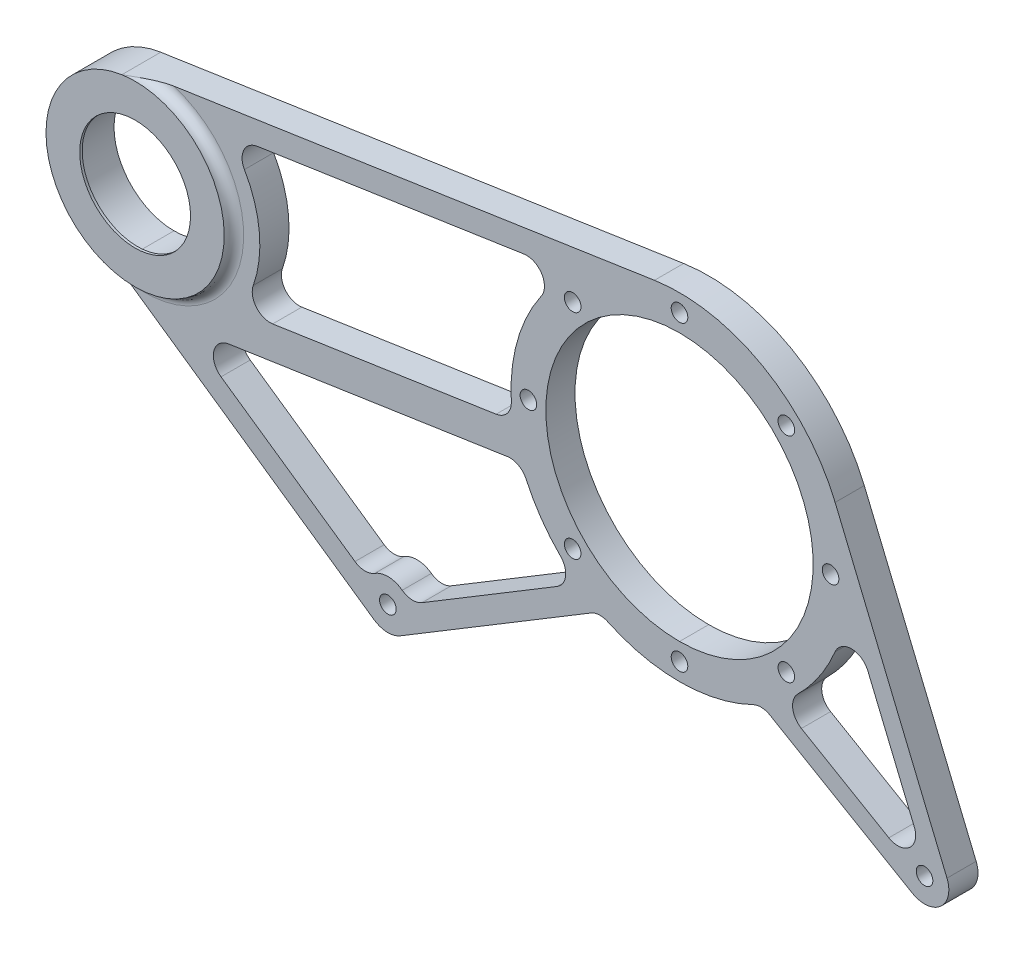
SolidWorks part; units mm, degrees
material "6061-T6 (SS)"
ref_plane "Front Plane" through (0, 0, 0) normal (0, 0, 1) x (1, 0, 0)
ref_plane "Top Plane" through (0, 0, 0) normal (0, 1, 0) x (1, 0, 0)
ref_plane "Right Plane" through (0, 0, 0) normal (1, 0, 0) x (0, 0, -1)
sketch "Sketch1" plane through (0, 0, 0) normal (0, 0, 1) x (1, 0, 0)
  line L0 (-329.0358, 136.1378) -> (-124.1059, 166.9079)
  line L1 (-343.7594, 72.9056) -> (-234.0298, -3.2296)
  line L2 (-223.6766, -3.5577) -> (-149.0272, 41.5159)
  line L3 (-114.3, 88.9) -> (-114.3, 101.6) construction
  line L4 (-53.3056, 126.9173) -> (-9.4675, 21.3025)
  line L5 (-23.0618, 9.4221) -> (-78.8665, 41.9532)
  circle A0 centre (-114.3, 88.9) radius 82.9716 construction
  circle A1 centre (-228.6, -20.8038) radius 12.7 construction
  circle A2 centre (0, 0) radius 12.7 construction
  circle A3 centre (-323.85, 101.6) radius 114 construction
  circle A4 centre (-323.85, 101.6) radius 23.5
  circle A5 centre (-114.3, 101.6) radius 52.3875
  arc A6 (-142.4404, 41.8555) -> (-85.4371, 42.2012) centre (-114.3, 101.6) ccw
  circle A7 centre (-323.85, 101.6) radius 34.925
  arc A8 (-223.6766, -3.5577) -> (-234.0298, -3.2296) centre (-228.6, 4.5962) cw
  arc A9 (-9.4675, 21.3025) -> (-23.0618, 9.4221) centre (-18.2648, 17.651) cw
  circle A10 centre (-228.6, 4.5962) radius 3.2512
  circle A11 centre (-18.2648, 17.651) radius 3.2512
  arc A12 (-142.4404, 41.8555) -> (-149.0272, 41.5159) centre (-145.4168, 35.5364) ccw
  arc A13 (-78.8665, 41.9532) -> (-85.4371, 42.2012) centre (-82.3843, 35.9187) ccw
  circle A14 centre (-114.3, 101.6) radius 66.04 construction
  arc A15 (-124.1059, 166.9079) -> (-53.3056, 126.9173) centre (-114.3, 101.6) cw
  point P33 (-145.0631, 160.0372)
  dimension "D1" = 88.9
  dimension "D2" = 12.7
  dimension "D3" = 25.4
  dimension "D4" = 25.4
  dimension "D8" = 165.9433
  dimension "D9" = 228
  dimension "D10" = 47
  dimension "D12" = 104.775
  dimension "D14" = 132.08
  dimension "D15" = 69.85
  dimension "D16" = 9.525
  dimension "D18" = 9.525
  dimension "D20" = 6.5024
  dimension "D21" = 6.5024
  dimension "D23" = 6.985
  dimension "D24" = 6.985
  dimension "D25" = 66.04
  dimension "D5" = 228.6
  dimension "D6" = 20.8038
  dimension "D7" = 114.3
  dimension "D11" = 12.7
  dimension "D13" = 209.55
  dimension "D17" = 25.4
  dimension "D19" = 25.4
  dimension "D22" = 17.651
extrude "Boss-Extrude1" add sketch "Sketch1" along normal blind 11.43 contours A7 A4 | A8 L2 A6 L0 A7 L1 A10 | A6 A5 | A9 L4 A6 L5 A11 region at (-187.4243, 81.6254, 0) region at (-301.706, 127.3172, 0)
ref_point "Point2"
ref_point "Point4"
ref_plane "Plane2" through (-114.3, 0, 0) normal (1, 0, 0) x (0, 0, -1)
ref_plane "Plane3" through (-323.85, 0, 0) normal (1, 0, 0) x (0, 0, -1)
sketch "Sketch5" plane through (0, 0, 11.43) normal (0, 0, 1) x (1, 0, 0)
  circle A0 centre (-323.85, 101.6) radius 23.5
  circle A1 centre (-323.85, 101.6) radius 34.925
extrude "Boss-Extrude3" add sketch "Sketch5" along normal blind 3.81
fillet "Fillet2" radius 3.81 1 edges at (-289.835, 93.6796, 11.43)
sketch "Sketch6" plane through (0, 0, 15.24) normal (0, 0, 1) x (1, 0, 0)
  circle A0 centre (-323.85, 101.6) radius 23.5
  circle A1 centre (-323.85, 101.6) radius 21.722
  dimension "D1" = 47
  dimension "D2" = 1.778
extrude "Boss-Extrude4" add sketch "Sketch6" against normal blind 0.9677
split line "Split Line3"
split line "Split Line4"
sketch "Sketch7" plane through (0, 0, 0) normal (0, 0, 1) x (1, 0, 0)
  line L0 (-279.7929, 134.542) -> (-175.2648, 150.2368)
  line L1 (-300.8405, 140.3714) -> (-125.2445, 166.737)
  line L2 (-312.4691, 138.6253) -> (-124.1059, 166.9079) construction
  line L3 (-329.9956, 63.3556) -> (-234.0298, -3.2296) construction
  line L4 (-329.9956, 63.3556) -> (-320.3344, 56.6523) construction
  line L5 (-293.9898, 49.1936) -> (-241.4832, 12.7622)
  line L6 (-215.2255, 11.93) -> (-162.2555, 43.9136)
  line L7 (-223.6766, -3.5577) -> (-149.0272, 41.5159) construction
  line L8 (-223.6766, -3.5577) -> (-149.0272, 41.5159) construction
  line L9 (-291.0451, 61.84) -> (-181.7958, 78.2437)
  line L10 (-273.7403, 77.2807) -> (-186.1633, 90.4303)
  line L11 (-32.2583, 23.6034) -> (-66.5305, 43.5822)
  line L12 (-22.2892, 32.3156) -> (-40.471, 76.1193)
  line L13 (-23.0618, 9.4221) -> (-78.8665, 41.9532) construction
  line L14 (-53.3056, 126.9173) -> (-9.4675, 21.3025) construction
  line L15 (-23.0618, 9.4221) -> (-78.8665, 41.9532) construction
  line L16 (-53.3056, 126.9173) -> (-9.4675, 21.3025) construction
  line L17 (-312.4691, 138.6253) -> (-124.1059, 166.9079) construction
  circle A0 centre (-114.3, 101.6) radius 62.0284 construction
  circle A1 centre (-323.85, 101.6) radius 38.735 construction
  circle A2 centre (-323.85, 101.6) radius 45.085 construction
  arc A4 (-291.0451, 61.84) -> (-293.9898, 49.1936) centre (-290.0079, 54.9325) ccw
  arc A5 (-174.4017, 74.231) -> (-160.9335, 54.839) centre (-114.3, 101.6) ccw
  arc A6 (-160.9335, 54.839) -> (-162.2555, 43.9136) centre (-165.8659, 49.8931) cw
  arc A7 (-181.7958, 78.2437) -> (-174.4017, 74.231) centre (-180.7586, 71.3362) cw
  arc A8 (-284.805, 124.142) -> (-281.3603, 86.524) centre (-323.85, 101.6) cw
  arc A9 (-168.4954, 139.3377) -> (-180.2274, 97.7456) centre (-114.3, 101.6) ccw
  arc A10 (-180.2274, 97.7456) -> (-186.1633, 90.4303) centre (-187.2005, 97.3379) cw
  arc A11 (-284.805, 124.142) -> (-279.7929, 134.542) centre (-278.7557, 127.6344) cw
  arc A12 (-281.3603, 86.524) -> (-273.7403, 77.2807) centre (-274.7774, 84.1883) ccw
  arc A13 (-175.2648, 150.2368) -> (-168.4954, 139.3377) centre (-174.2276, 143.3292) cw
  arc A14 (-222.9669, 12.2769) -> (-233.7354, 12.6182) centre (-228.6, 4.5962) ccw
  arc A15 (-223.6766, -3.5577) -> (-223.0453, -3.1415) centre (-228.6, 4.5962) ccw
  arc A16 (-233.7354, 12.6182) -> (-241.4832, 12.7622) centre (-237.5013, 18.5011) cw
  arc A17 (-215.2255, 11.93) -> (-222.9669, 12.2769) centre (-218.836, 17.9095) cw
  arc A19 (-22.2892, 32.3156) -> (-32.2583, 23.6034) centre (-28.7405, 29.6379) cw
  arc A20 (-67.9184, 54.589) -> (-53.3671, 76.135) centre (-114.3, 101.6) ccw
  arc A21 (-40.471, 76.1193) -> (-53.3671, 76.135) centre (-46.9223, 73.4415) ccw
  arc A22 (-66.5305, 43.5822) -> (-67.9184, 54.589) centre (-63.0127, 49.6167) cw
  circle A23 centre (-114.3, 101.6) radius 66.04 construction
  point P31 (-308.45, 59.2267)
  point P33 (-172.4396, 79.9826)
  point P41 (-291.3157, 132.8118)
  point P45 (-154.09, 149.1844)
  point P64 (-78.8001, 50.7347)
  dimension "D1" = 6.35
  dimension "D3" = 8.89
  dimension "D5" = 90.17
  dimension "D6" = 124.0568
  dimension "D7" = 6.985
  dimension "D8" = 6.985
  dimension "D10" = 6.985
  dimension "D11" = 9.525
  dimension "D12" = 6.985
  dimension "D13" = 6.985
  dimension "D16" = 6.985
  dimension "D17" = 132.08
  dimension "D2" = 8.89
  dimension "D4" = 8.89
  dimension "D9" = 12.7
  dimension "D14" = 7.62
  dimension "D15" = 7.62
extrude "Cut-Extrude2" cut sketch "Sketch7" against normal through all both and the other way through all contours A17 L6 A6 A5 A7 L9 A4 L5 A16 A14 | A13 L0 A11 A8 A12 L10 A10 A9 | A22 L11 A19 L12 A21 A20 | A21 A20 A22 L11 A19 L12 region at (-228.3297, 114.1645, 0) region at (-224.0506, 46.8096, 0) region at (-44.9997, 50.0307, 0)
sketch "Sketch8" plane through (0, 0, 11.43) normal (0, 0, 1) x (1, 0, 0)
  line L0 (-114.3, 101.6) -> (-114.3, 160.8137) construction
  circle A0 centre (-114.3, 101.6) radius 59.2137 construction
  circle A1 centre (-114.3, 160.8137) radius 3.2512
  circle A2 centre (-72.4296, 143.4704) radius 3.2512
  circle A3 centre (-55.0862, 101.6) radius 3.2512
  circle A4 centre (-72.4296, 59.7296) radius 3.2512
  circle A5 centre (-114.3, 42.3863) radius 3.2512
  circle A6 centre (-156.1704, 59.7296) radius 3.2512
  circle A7 centre (-173.5137, 101.6) radius 3.2512
  circle A8 centre (-156.1704, 143.4704) radius 3.2512
  point P22 (-114.3, 101.6)
  dimension "D1" = 118.4275
  dimension "D2" = 6.5024
  dimension "D3" = 8
extrude "Cut-Extrude3" cut sketch "Sketch8" against normal through all both and the other way through all
